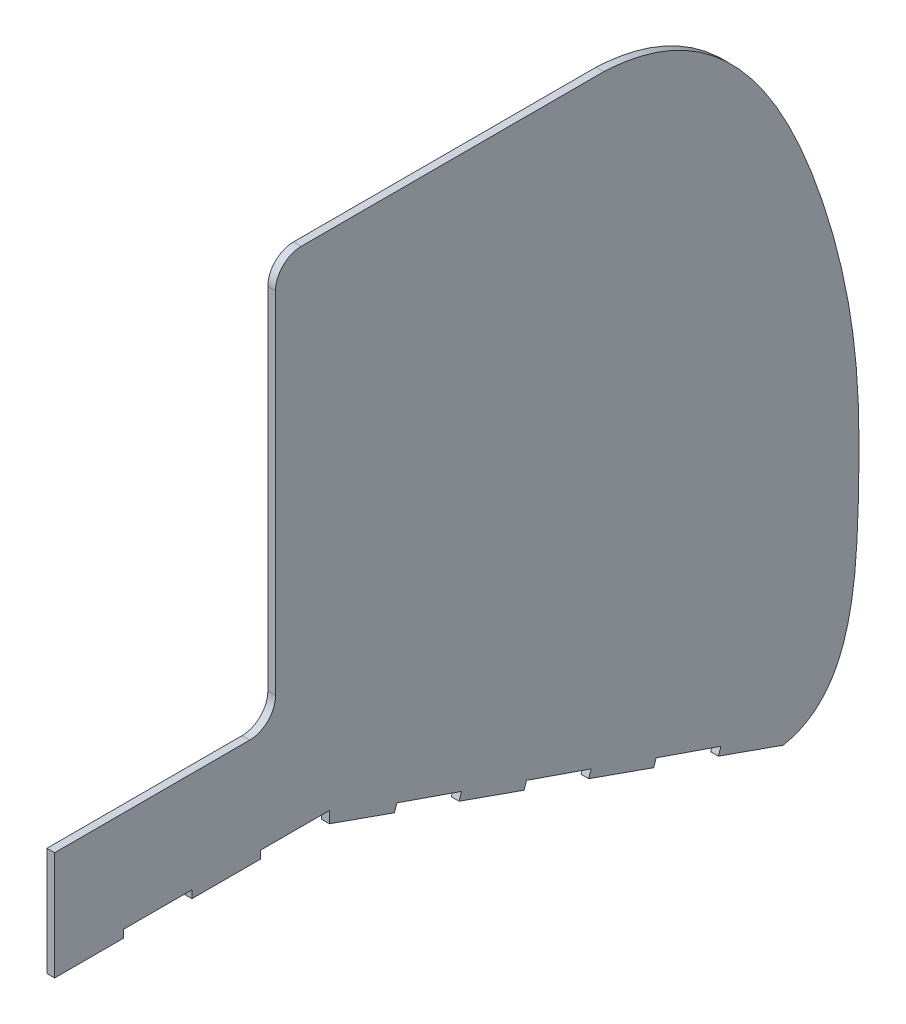
SolidWorks part; units mm, degrees
ref_plane "Front Plane" through (0, 0, 0) normal (0, 0, 1) x (1, 0, 0)
ref_plane "Top Plane" through (0, 0, 0) normal (0, 1, 0) x (1, 0, 0)
ref_plane "Right Plane" through (0, 0, 0) normal (1, 0, 0) x (0, 0, -1)
sketch "Sketch1" plane through (0, 0, 0) normal (1, 0, 0) x (0, 0, -1)
  line L5 (0, 0) -> (0, -59) construction
  line L6 (0, 0) -> (0, 196.9217) construction
  line L13 (-127.6733, 50.6216) -> (-127.6733, 186.9217)
  line L14 (-117.6733, 196.9217) -> (0, 196.9217)
  line L20 (-213.6, -1.5783) -> (-213.6, 40.6217)
  line L21 (-213.6, 40.6217) -> (-137.7211, 40.6217)
  line L57 (-106.7215, 1.4217) -> (-133.5, 1.4217)
  line L58 (-133.5, 1.4217) -> (-133.5, -1.5783)
  line L60 (-133.5, -1.5783) -> (-160.2, -1.5783)
  line L61 (-160.2, -1.5783) -> (-160.2, 1.4217)
  line L62 (-160.2, 1.4217) -> (-186.9, 1.4217)
  line L63 (-186.9, 1.4217) -> (-186.9, -1.5783)
  line L64 (-186.9, -1.5783) -> (-213.6, -1.5783)
  line L69 (-106.7215, 1.4217) -> (-106.7215, -3.0783)
  line L70 (-106.7215, -3.0783) -> (57.8709, -61.1762) construction
  line L71 (-106.7215, -3.0783) -> (-81.4531, -11.9975)
  line L72 (-81.4531, -11.9975) -> (-80.4723, -9.1624)
  line L73 (-56.2889, -20.7022) -> (-31.0205, -29.6214)
  line L74 (-31.0205, -29.6214) -> (-30.0397, -26.7863)
  line L75 (-5.8563, -38.3261) -> (19.4122, -47.2453)
  line L76 (19.4122, -47.2453) -> (20.3929, -44.4102)
  line L77 (44.5763, -55.95) -> (69.8448, -64.8692)
  line L79 (-80.4723, -9.1624) -> (-55.3082, -17.867)
  line L80 (-55.3082, -17.867) -> (-56.2889, -20.7022)
  line L81 (-30.0397, -26.7863) -> (-4.8756, -35.4909)
  line L82 (-4.8756, -35.4909) -> (-5.8563, -38.3261)
  line L83 (20.3929, -44.4102) -> (45.557, -53.1148)
  line L84 (45.557, -53.1148) -> (44.5763, -55.95)
  line L86 (69.8448, -64.8692) -> (70.8255, -62.0341) [skipped]
  arc A1 (-127.6733, 186.9217) -> (-117.6733, 196.9217) centre (-117.6733, 186.9217) cw
  arc A3 (-137.7211, 40.6217) -> (-127.6733, 50.6216) centre (-137.6733, 50.6216) ccw
  spline S0 degree 3 poles (0, 196.9217) (46.1968, 194.8557) (79.8849, 137.404) (99.1822, 59.2088) (100.053, 0.3036) (95.625, -59.9104) (69.8448, -64.8692) knots 0 0 0 0 0.394606 0.564234 0.764369 1 1 1 1
  point P16 (45.4215, 224.6598)
  point P17 (70.7136, 205.4318)
  point P19 (78.2365, -62.2768)
  point P24 (77.3102, -62.3864)
  point P26 (0, 0)
  point P28 (0, 0)
  point P30 (45.4215, 172.8009)
  point P33 (70.3347, 152.2498)
  point P34 (98.9357, 0)
  point P35 (-127.6733, 60.0336)
  point P37 (45.4215, 158.3586)
  point P39 (67.2298, 147.5195)
  point P40 (96.5594, 62.7188)
  point P42 (83.8074, 114.3643)
  point P46 (45.4215, 151.5466)
  point P48 (-106.5923, -3.2125)
  point P50 (37.5877, 160.7545)
  point P56 (35.0861, 175.7644)
  point P57 (40.2895, 182.719)
  point P58 (0, 0)
  dimension "D3" = 42.2
  dimension "D1" = 10
  dimension "D2" = 10
  dimension "D4" = 4
  dimension "D5" = 26.7
  dimension "D6" = 3
  dimension "D7" = 3
  dimension "D8" = 200
extrude "Boss-Extrude1" add sketch "Sketch1" along normal blind 3
